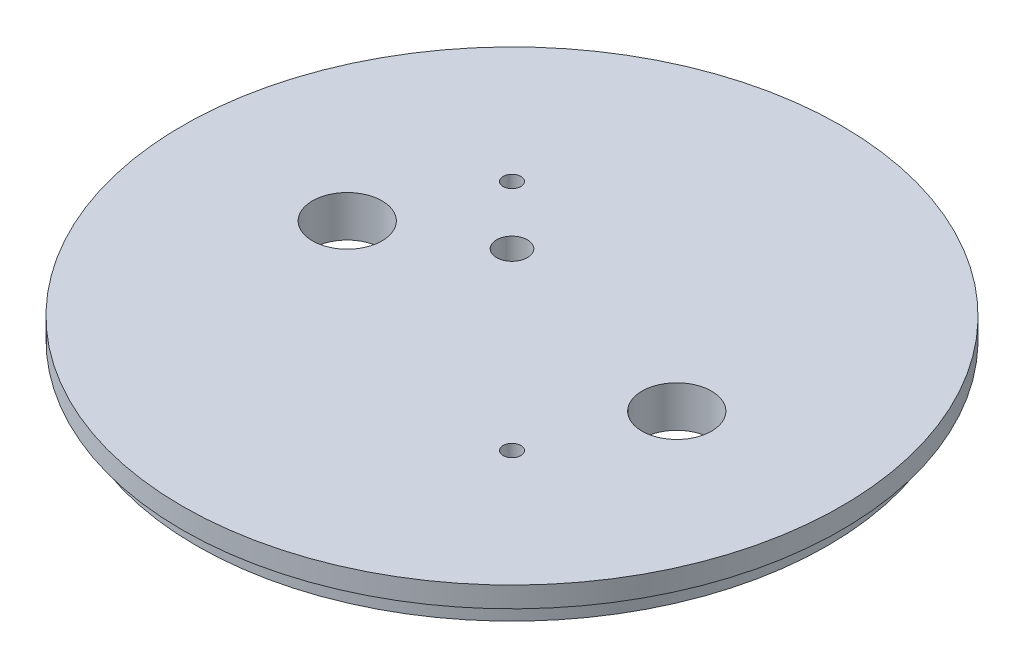
SolidWorks part; units mm, degrees
material "6061-T4 (SS)"
ref_plane "Front Plane" through (0, 0, 0) normal (0, 0, 1) x (1, 0, 0)
ref_plane "Top Plane" through (0, 0, 0) normal (0, 1, 0) x (1, 0, 0)
ref_plane "Right Plane" through (0, 0, 0) normal (1, 0, 0) x (0, 0, -1)
sketch "Sketch1" plane through (0, 0, 0) normal (0, 1, 0) x (1, 0, 0)
  line L0 (0, -50.8) -> (0, 50.8) construction
  line L1 (-50.8, 0) -> (50.8, 0) construction
  line L2 (-17.9605, 17.9605) -> (0, 0) construction
  line L3 (0, 56.7387) -> (0, 29.6936) construction
  line L4 (3.6407, 56.7387) -> (3.6407, 29.6936) construction
  line L5 (-3.6407, 56.7387) -> (-3.6407, 29.6936) construction
  line L6 (0, -56.7387) -> (0, -29.6936) construction
  line L7 (3.6407, -56.7387) -> (3.6407, -29.6936) construction
  line L8 (-3.6407, -56.7387) -> (-3.6407, -29.6936) construction
  line L9 (-35.921, -35.921) -> (54.3236, 54.3236) construction
  circle A0 centre (0, 0) radius 50.8
  circle A1 centre (0, 0) radius 3.175 construction
  circle A2 centre (25.4, 0) radius 5.3578
  circle A3 centre (-25.4, 0) radius 5.3578
  circle A4 centre (-17.9605, 17.9605) radius 1.3589
  arc A6 (3.6407, 56.7387) -> (-3.6407, 56.7387) centre (0, 56.7387) ccw construction
  arc A7 (-3.6407, 29.6936) -> (3.6407, 29.6936) centre (0, 29.6936) ccw construction
  arc A8 (3.6407, -56.7387) -> (-3.6407, -56.7387) centre (0, -56.7387) cw construction
  arc A9 (-3.6407, -29.6936) -> (3.6407, -29.6936) centre (0, -29.6936) cw construction
  circle A10 centre (17.9605, -17.9605) radius 1.3589
  circle A11 centre (-8.9803, 8.9803) radius 2.3813
  circle A12 centre (8.9803, -8.9803) radius 2.3813 construction
  point P16 (0, 43.2162)
  point P19 (0, 0)
  point P26 (0, -43.2162)
  dimension "D1" = 101.6
  dimension "D2" = 6.35
  dimension "D3" = 10.7156
  dimension "D5" = 2.7178
  dimension "D8" = 4.7625
  dimension "D6" = 25.4
  dimension "D7" = 45
  dimension "D4" = 45
  dimension "D9" = 25.4
extrude "Boss-Extrude1" add sketch "Sketch1" along normal blind 6.35
sketch "Sketch2" plane through (0, 0, 0) normal (0, -1, 0) x (1, 0, 0)
  circle A0 centre (0, 0) radius 50.8
  circle A1 centre (0, 0) radius 48.641
  dimension "D1" = 101.6
  dimension "D2" = 97.282
extrude "Cut-Extrude1" cut sketch "Sketch2" against normal blind 3.175
sketch "Sketch3" plane through (0, 6.35, 0) normal (0, 1, 0) x (1, 0, 0)
  line L0 (0, 50.8) -> (0, -50.8) construction
  line L1 (-50.8, 0) -> (50.8, 0) construction
  line L2 (0, 34.798) -> (0, 13.97) construction
  line L3 (3.2385, 34.798) -> (3.2385, 13.97)
  line L4 (-3.2385, 34.798) -> (-3.2385, 13.97)
  line L5 (0, -34.798) -> (0, -13.97) construction
  line L6 (3.2385, -34.798) -> (3.2385, -13.97)
  line L7 (-3.2385, -34.798) -> (-3.2385, -13.97)
  circle A0 centre (0, 0) radius 50.8 construction
  arc A1 (3.2385, 34.798) -> (-3.2385, 34.798) centre (0, 34.798) ccw
  arc A2 (-3.2385, 13.97) -> (3.2385, 13.97) centre (0, 13.97) ccw
  arc A3 (3.2385, -34.798) -> (-3.2385, -34.798) centre (0, -34.798) cw
  arc A4 (-3.2385, -13.97) -> (3.2385, -13.97) centre (0, -13.97) cw
  point P7 (0, 13.97)
  point P8 (0, 34.798)
  point P12 (0, 24.384)
  point P20 (0, -24.384)
  point P25 (0, -34.798)
  point P26 (0, -13.97)
  dimension "D1" = 13.97
  dimension "D2" = 20.828
  dimension "D3" = 6.477
extrude "Cut-Extrude2" cut sketch "Sketch3" against normal blind 3.81 from offset 2.794 offset against normal yes
equation "\"Coupler_OD\" = 3.899in"
equation "\"Coupler_ID\" = 3.755in"
equation "\"Lead_Screw_Hole_Diam\" = (27/64)*1in"
equation "\"Lead_Screw_Dist\" = 2in"
equation "\"D9@Sketch1\"=\"Lead_Screw_Dist\"/2"
equation "\"D3@Sketch1\"=\"Lead_Screw_Hole_Diam\""
